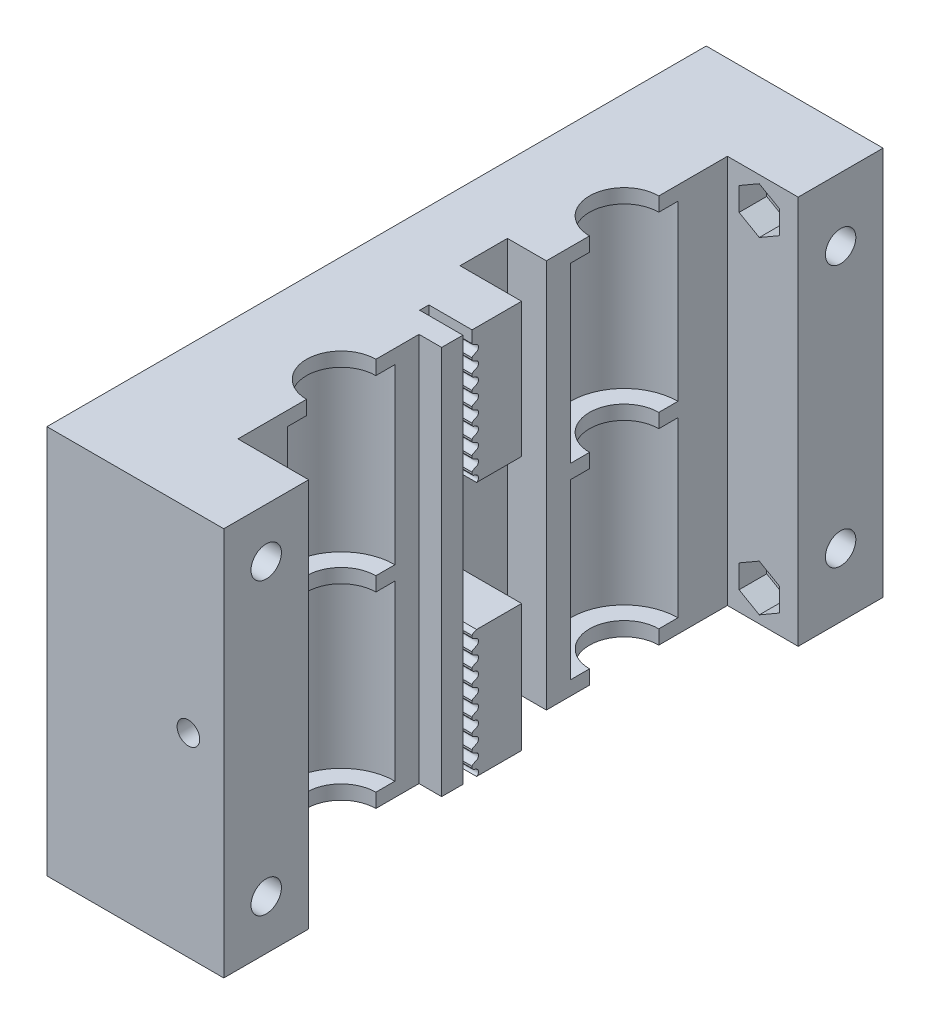
SolidWorks part; units mm, degrees
ref_plane "Front Plane" through (0, 0, 0) normal (0, 0, 1) x (1, 0, 0)
ref_plane "Top Plane" through (0, 0, 0) normal (0, 1, 0) x (1, 0, 0)
ref_plane "Right Plane" through (0, 0, 0) normal (1, 0, 0) x (0, 0, -1)
sketch "Sketch1" plane through (0, 0, 0) normal (0, 1, 0) x (1, 0, 0)
  line L0 (0, 36.6) -> (0, 43.6)
  line L1 (0, 43.6) -> (10, 43.6)
  line L2 (10, 43.6) -> (10, 55.6)
  line L3 (10, 55.6) -> (-15, 55.6)
  line L5 (-15, -37.6) -> (10, -37.6)
  line L6 (10, -37.6) -> (10, -25.6)
  line L7 (10, -25.6) -> (0, -25.6)
  line L8 (0, -25.6) -> (0, -18.6)
  line L9 (0, 21.4) -> (0, -3.4) construction
  line L10 (0, 18) -> (-5.5, 18)
  line L11 (-5.5, 18) -> (-5.5, 0)
  line L12 (-5.5, 0) -> (0, 0)
  line L24 (-15, 55.6) -> (-15, -37.6)
  line L25 (0, 0) -> (0, -3.4)
  line L26 (0, 18) -> (0, 21.4)
  arc A1 (0, 21.4) -> (0, 36.6) centre (0, 29) cw
  arc A2 (0, -18.6) -> (0, -3.4) centre (0, -11) cw
  dimension "D2" = 7.6
  dimension "D3" = 7.6
  dimension "D4" = 7
  dimension "D5" = 7
  dimension "D6" = 12
  dimension "D7" = 12
  dimension "D8" = 18
  dimension "D9" = 10
  dimension "D10" = 10
  dimension "D11" = 5.5
  dimension "D12" = 3.4
  dimension "D13" = 3.4
  dimension "D14" = 25
  dimension "D15" = 40
extrude "Boss-Extrude1" add sketch "Sketch1" along normal blind 55
sketch "Sketch2" plane through (0, 0, 0) normal (0, -1, 0) x (1, 0, 0)
  line L0 (0, 18.6) -> (0, 15.9)
  line L1 (0, 6.1) -> (0, 3.4)
  line L2 (0, -21.4) -> (0, -24.102)
  line L3 (0, -33.898) -> (0, -36.6)
  arc A0 (0, 3.4) -> (0, 18.6) centre (0, 11) cw
  arc A1 (0, 6.1) -> (0, 15.9) centre (0, 11) cw
  arc A2 (0, -36.6) -> (0, -21.4) centre (0, -29) cw
  arc A3 (0, -33.898) -> (0, -24.102) centre (0, -29) cw
  dimension "D1" = 4.9
  dimension "D2" = 4.898
extrude "Boss-Extrude2" add sketch "Sketch2" against normal blind 2
ref_plane "Plane1" through (0, 26.5, 0) normal (0, -1, 0) x (-1, 0, 0)
sketch "Sketch3" plane through (0, 26.5, 0) normal (0, -1, 0) x (-1, 0, 0)
  line L0 (0, -3.4) -> (0, -6.1)
  line L1 (0, -15.9) -> (0, -18.6)
  line L2 (0, 21.4) -> (0, 24.1)
  line L3 (0, 33.9) -> (0, 36.6)
  arc A0 (0, -18.6) -> (0, -3.4) centre (0, -11) ccw
  arc A1 (0, -15.9) -> (0, -6.1) centre (0, -11) ccw
  arc A2 (0, 36.6) -> (0, 21.4) centre (0, 29) cw
  arc A3 (0, 24.1) -> (0, 33.9) centre (0, 29) ccw
  dimension "D1" = 4.9
extrude "Boss-Extrude3" add sketch "Sketch3" against normal blind 2
ref_plane "Plane2" through (0, 53, 0) normal (0, -1, 0) x (-1, 0, 0)
sketch "Sketch4" plane through (0, 53, 0) normal (0, -1, 0) x (-1, 0, 0)
  line L0 (0, -18.6) -> (0, -15.9)
  line L1 (0, -6.1) -> (0, -3.4)
  line L2 (0, 36.6) -> (0, 33.9)
  line L3 (0, 24.1) -> (0, 21.4)
  arc A0 (0, -3.4) -> (0, -18.6) centre (0, -11) cw
  arc A1 (0, -15.9) -> (0, -6.1) centre (0, -11) ccw
  arc A2 (0, -15.9) -> (0, -6.1) centre (0, -11) ccw construction
  arc A3 (0, 21.4) -> (0, 36.6) centre (0, 29) ccw construction
  arc A5 (0, 24.1) -> (0, 33.9) centre (0, 29) ccw
  arc A6 (0, 21.4) -> (0, 36.6) centre (0, 29) ccw
  arc A7 (0, 24.1) -> (0, 33.9) centre (0, 29) ccw construction
extrude "Boss-Extrude4" add sketch "Sketch4" against normal blind 2
sketch "Sketch7" plane through (0, 55, 0) normal (0, 1, 0) x (1, 0, 0)
  line L0 (0, 0) -> (3.2, 0)
  line L1 (3.2, 0) -> (3.2, -2)
  line L2 (3.2, -2) -> (0, -2)
  line L3 (0, -6.1) -> (0, 0) construction
  line L4 (0, -2) -> (0, 0)
  dimension "D1" = 2
  dimension "D2" = 3.2
extrude "Boss-Extrude5" add sketch "Sketch7" against normal up to surface (55 mm away) up to face at (-0.6749, 0, -9)
sketch "Sketch8" plane through (0, 55, 0) normal (0, 1, 0) x (1, 0, 0)
  line L0 (0, 18) -> (0, 0) construction
  line L1 (-3.9424, 9) -> (6.0186, 9) construction
  line L2 (-5.5, 0) -> (3.2, 0)
  line L3 (3.2, 0) -> (-5.5, 0) construction
  line L4 (3.2, 0) -> (3.2, 3)
  line L5 (3.2, 3) -> (-5.5, 3)
  line L6 (-5.5, 0) -> (-5.5, 18) construction
  line L7 (-5.5, 3) -> (-5.5, 0)
  line L8 (3.2, -2) -> (3.2, 0) construction
  line L9 (-5.5, 11.3) -> (3.2, 11.3)
  line L10 (3.2, 11.3) -> (3.2, 4.3)
  line L11 (3.2, 4.3) -> (-5.5, 4.3)
  line L12 (-5.5, 4.3) -> (-5.5, 11.3)
  point P6 (0, 9)
  dimension "D1" = 3
  dimension "D2" = 7
  dimension "D3" = 1.3
extrude "Boss-Extrude6" add sketch "Sketch8" against normal up to surface (55 mm away) up to face at (-0.2443, 0, -7.7778)
sketch "Sketch11" plane through (3.2, 0, 0) normal (1, 0, 0) x (0, 0, -1)
  line L0 (1264.5675, 560.6102) -> (1262.5675, 560.6102) construction
  line L1 (4.3, 0) -> (4.3, 55) construction
  line L2 (4.2853, 45.4328) -> (4.2853, 47.4569)
  spline S0 degree 3 poles (4.2853, 47.4569) (4.284, 47.4147) (4.2867, 47.3463) (4.3158, 47.2523) (4.3712, 47.1708) (4.4771, 47.1012) (4.6041, 47.0544) (4.7214, 46.9971) (4.8254, 46.9474) (4.9241, 46.9047) (5.0186, 46.8525) (5.1086, 46.7783) (5.1561, 46.6816) (5.1905, 46.5926) (5.1913, 46.5195) (5.1931, 46.4561) (5.1891, 46.3829) (5.1871, 46.2871) (5.1399, 46.1709) (5.0494, 46.057) (4.9087, 45.9856) (4.7554, 45.916) (4.621, 45.8529) (4.5075, 45.8004) (4.4122, 45.7562) (4.3028, 45.6419) (4.2855, 45.5136) (4.2853, 45.4328) knots 0 0 0 0 0.042789 0.068472 0.09859 0.140403 0.193951 0.235463 0.272242 0.310543 0.344117 0.381404 0.42616 0.451184 0.477135 0.499165 0.515432 0.551275 0.595353 0.639476 0.695379 0.752126 0.810504 0.845135 0.878871 0.916023 1 1 1 1
  line M5 (4.3, 55) -> (4.3, 0)
  dimension "D1" = 2
extrude "Cut-Extrude4" cut sketch "Sketch11" against normal up to surface (8.7 mm away) contours S0 M5 region at (3.2, 46.4474, -4.673) up to face at (-5.5, 27.5, -3.65)
pattern_linear "LPattern1" count 24 spacing 2 along (0, -1, 0) count 4 spacing 2 along (0, 1, 0) of "Cut-Extrude4"
sketch "Sketch12" plane through (3.2, 0, 0) normal (1, 0, 0) x (0, 0, -1)
  line L0 (11.3, 0) -> (11.3, 55) construction
  line L1 (11.3, 36) -> (4.3, 36)
  line L2 (11.3, 36) -> (11.3, 18)
  line L3 (11.3, 18) -> (4.3, 18)
  line L4 (4.3, 36) -> (4.3, 18)
  dimension "D1" = 18
  dimension "D2" = 19
extrude "Cut-Extrude5" cut sketch "Sketch12" against normal up to surface (8.7 mm away) up to face at (-5.5, 27.5, -14.65)
sketch "Sketch13" plane through (0, 55, 0) normal (0, 1, 0) x (1, 0, 0)
  line L0 (-5.5, 3) -> (-2.9059, 3)
  line L1 (3.2, 3) -> (-5.5, 3) construction
  line L6 (-2.9059, 3) -> (-2.9059, 7.169)
  line L7 (-2.9059, 7.169) -> (-5.5, 7.169)
  line L8 (-5.5, 18) -> (-5.5, 0) construction
  line L9 (-5.5, 7.169) -> (-5.5, 3)
extrude "Boss-Extrude16" add sketch "Sketch13" against normal up to surface (55 mm away) up to face at (-0.409, 0, -8.1123)
sketch "Sketch14" plane through (0, 55, 0) normal (0, 1, 0) x (1, 0, 0)
  line L0 (0, 0) -> (0, -2)
  line L1 (0, -2) -> (3.2, -2)
  line L2 (3.2, -2) -> (3.2, 0)
  line L3 (3.2, -2) -> (3.2, 3) construction
  line L4 (3.2, 0) -> (0, 0)
extrude "Cut-Extrude6" cut sketch "Sketch14" against normal up to surface (55 mm away) up to face at (-0.1732, 0, -8.1123)
sketch "Sketch16" plane through (-2.9059, 0, 0) normal (1, 0, 0) x (0, 0, -1)
  line L0 (7.169, 36) -> (3, 36)
  line L1 (3, 0) -> (3, 55) construction
  line L2 (7.169, 18) -> (3, 18)
  line L3 (3, 18) -> (3, 36)
  line L4 (7.169, 36) -> (7.169, 18)
extrude "Cut-Extrude7" cut sketch "Sketch16" against normal up to surface (2.5941 mm away) up to face at (-5.5, 27.25, -11.9423)
sketch "Sketch17" plane through (-15, 0, 0) normal (-1, 0, 0) x (0, 0, 1)
  line L0 (-55.6, 55) -> (37.6, 55) construction
  line L1 (37.6, 55) -> (37.6, 0) construction
  line L2 (37.6, 0) -> (25.6, 0) construction
  line L3 (-36.6, 0) -> (-43.6, 0) construction
  line L4 (-55.6, 55) -> (-55.6, 0) construction
  circle A0 centre (31.6, 48) radius 2.15
  circle A1 centre (31.6, 7) radius 2.15
  circle A2 centre (-49.6, 9) radius 2.15
  circle A3 centre (-49.6, 46) radius 2.15
  dimension "D1" = 4.3
  dimension "D2" = 4.3
  dimension "D3" = 4.3
  dimension "D4" = 4.3
  dimension "D6" = 6
  dimension "D7" = 7
  dimension "D5" = 7
  dimension "D8" = 6
  dimension "D9" = 9
  dimension "D10" = 6
  dimension "D11" = 6
  dimension "D12" = 9
extrude "Cut-Extrude8" cut sketch "Sketch17" against normal up to surface (25 mm away) up to face at (10, 27.5, 31.6)
ref_plane "Plane3" through (-11.9, 0, 0) normal (-1, 0, 0) x (0, 0, 1)
sketch "Sketch20" plane through (-5.5, 0, 0) normal (1, 0, 0) x (0, 0, -1)
  line L0 (55.6, 55) -> (-37.6, 55) construction
  line L1 (55.6, 55) -> (55.6, 0) construction
  circle A0 centre (9, 27.5) radius 2.7
  dimension "D1" = 5.4
  dimension "D2" = 27.5
  dimension "D3" = 46.6
extrude "Cut-Extrude9" cut sketch "Sketch20" against normal up to surface (9.5 mm away) up to face at (-15, 46, -47.45)
sketch "Sketch21" plane through (0, 0, -43.6) normal (0, 0, 1) x (1, 0, 0)
  line L0 (10, 55) -> (10, 0) construction
  line L1 (4.5, 47.3091) -> (7.35, 48.9546)
  line L2 (7.35, 48.9546) -> (7.35, 52.2454)
  line L3 (7.35, 52.2454) -> (4.5, 53.8909)
  line L4 (4.5, 53.8909) -> (1.65, 52.2454)
  line L5 (1.65, 52.2454) -> (1.65, 48.9546)
  line L6 (1.65, 48.9546) -> (4.5, 47.3091)
  line L7 (0, 55) -> (10, 55) construction
  circle A0 centre (4.5, 50.6) radius 2.85 construction
  dimension "D2" = 4.4
  dimension "D3" = 5.5
  dimension "D1" = 5.7
ref_plane "Plane4" through (0, 27.5, 0) normal (0, 1, 0) x (1, 0, 0)
extrude "Cut-Extrude10" cut sketch "Sketch21" against normal blind 3.9
sketch "Sketch23" plane through (0, 0, -47.5) normal (0, 0, 1) x (1, 0, 0)
  line L0 (0, 55) -> (10, 55) construction
  line L1 (10, 55) -> (10, 0) construction
  circle A0 centre (4.5, 50.6) radius 1.6
  dimension "D1" = 3.2
  dimension "D2" = 4.4
  dimension "D3" = 5.5
extrude "Cut-Extrude11" cut sketch "Sketch23" against normal up to surface (8.1 mm away) up to face at (-2.5, 27.5, -55.6)
mirror "Mirror1" about plane through (0, 27.5, 0) normal (0, 1, 0) of "Cut-Extrude11", "Cut-Extrude10"
sketch "Sketch26" plane through (0, 0, 25.6) normal (0, 0, -1) x (-1, 0, 0)
  line L0 (-10, 55) -> (-10, 0) construction
  line L1 (-5, 24.2091) -> (-2.15, 25.8546)
  line L2 (-2.15, 25.8546) -> (-2.15, 29.1454)
  line L3 (-2.15, 29.1454) -> (-5, 30.7909)
  line L4 (-5, 30.7909) -> (-7.85, 29.1454)
  line L5 (-7.85, 29.1454) -> (-7.85, 25.8546)
  line L6 (-7.85, 25.8546) -> (-5, 24.2091)
  line L7 (-10, 0) -> (0, 0) construction
  circle A0 centre (-5, 27.5) radius 2.85 construction
  dimension "D1" = 27.5
  dimension "D2" = 5
  dimension "D3" = 5.7
extrude "Cut-Extrude12" cut sketch "Sketch26" against normal blind 4
sketch "Sketch27" plane through (0, 0, 29.6) normal (0, 0, -1) x (-1, 0, 0)
  line L0 (-10, 55) -> (-10, 0) construction
  line L1 (-10, 55) -> (0, 55) construction
  circle A0 centre (-5, 27.5) radius 1.6
  dimension "D3" = 3.2
  dimension "D1" = 5
  dimension "D2" = 27.5
extrude "Cut-Extrude13" cut sketch "Sketch27" against normal up to surface (8 mm away) up to face at (-2.5, 27.5, 37.6)
sketch "Sketch28" plane through (-15, 0, 0) normal (-1, 0, 0) x (0, 0, 1)
  line L0 (-55.6, 55) -> (-55.6, 0) construction
  line L1 (-45.95, 11.1073) -> (-49.6, 13.2147)
  line L2 (-49.6, 13.2147) -> (-53.25, 11.1073)
  line L3 (-53.25, 11.1073) -> (-53.25, 6.8927)
  line L4 (-53.25, 6.8927) -> (-49.6, 4.7853)
  line L5 (-49.6, 4.7853) -> (-45.95, 6.8927)
  line L6 (-45.95, 6.8927) -> (-45.95, 11.1073)
  circle A0 centre (-49.6, 9) radius 3.65 construction
  dimension "D1" = 7.3
extrude "Cut-Extrude14" cut sketch "Sketch28" against normal blind 4
pattern_linear "LPattern4" count 2 spacing 37 along (0, 1, 0) of "Cut-Extrude14"
sketch "Sketch29" plane through (-15, 0, 0) normal (-1, 0, 0) x (0, 0, 1)
  line L0 (37.6, 55) -> (37.6, 0) construction
  line L1 (31.6, 11.2147) -> (27.95, 9.1073)
  line L2 (27.95, 9.1073) -> (27.95, 4.8927)
  line L3 (27.95, 4.8927) -> (31.6, 2.7853)
  line L4 (31.6, 2.7853) -> (35.25, 4.8927)
  line L5 (35.25, 4.8927) -> (35.25, 9.1073)
  line L6 (35.25, 9.1073) -> (31.6, 11.2147)
  circle A0 centre (31.6, 7) radius 3.65 construction
  point P11 (35.25, 7)
  dimension "D1" = 7.3
extrude "Cut-Extrude15" cut sketch "Sketch29" against normal blind 4
pattern_linear "LPattern5" count 2 spacing 41 along (0, 1, 0) of "Cut-Extrude15"
ref_plane "Plane5" through (0, 0, -53.7) normal (0, 0, -1) x (-1, 0, 0)
